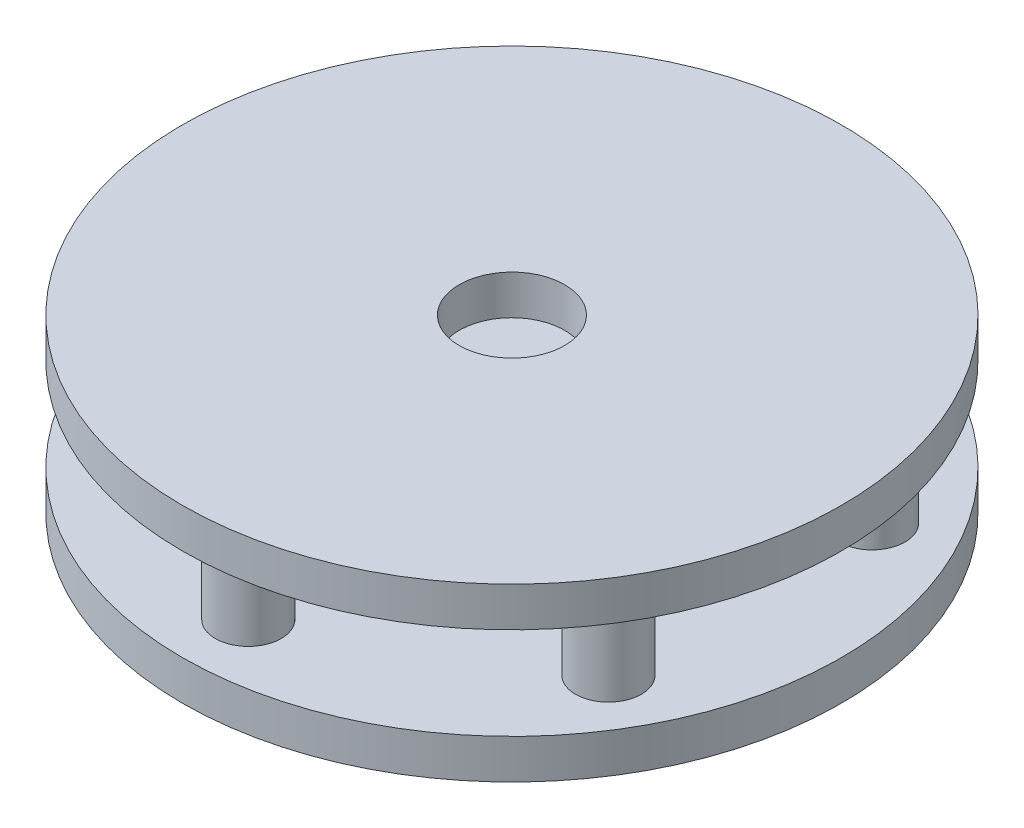
SolidWorks part; units mm, degrees
ref_plane "Front Plane" through (0, 0, 0) normal (0, 0, 1) x (1, 0, 0)
ref_plane "Top Plane" through (0, 0, 0) normal (0, 1, 0) x (1, 0, 0)
ref_plane "Right Plane" through (0, 0, 0) normal (1, 0, 0) x (0, 0, -1)
sketch "Sketch1" plane through (0, 0, 0) normal (0, 1, 0) x (1, 0, 0)
  circle A0 centre (0, 0) radius 25
  dimension "D1" = 50
extrude "Boss-Extrude1" add sketch "Sketch1" along normal blind 3
sketch "Sketch3" plane through (0, 3, 0) normal (0, 1, 0) x (1, 0, 0)
  line L0 (0, 20) -> (0, 0)
  circle A0 centre (0, 20) radius 2.5
  dimension "D1" = 5
  dimension "D2" = 20
extrude "Boss-Extrude2" add sketch "Sketch3" along normal blind 7 contours A0 region at (1.7178, 3, -18.2822)
pattern_circular "CirPattern1" count 6 over 360 about axis through (0, 3, 0) along (0, 1, 0) of "Boss-Extrude2"
sketch "Sketch4" plane through (0, 10, 0) normal (0, 1, 0) x (1, 0, 0)
  line L0 (-17.3205, -10) -> (0, 0)
  circle A0 centre (0, 0) radius 25
  dimension "D1" = 50
extrude "Boss-Extrude3" add sketch "Sketch4" along normal blind 3 contours A0
sketch "Sketch6" plane through (0, 13, 0) normal (0, 1, 0) x (1, 0, 0)
  circle A0 centre (0, 0) radius 4
  dimension "D1" = 8
extrude "Cut-Extrude1" cut sketch "Sketch6" against normal through all
sketch "Sketch8" plane through (0, 13, 0) normal (0, 1, 0) x (1, 0, 0)
